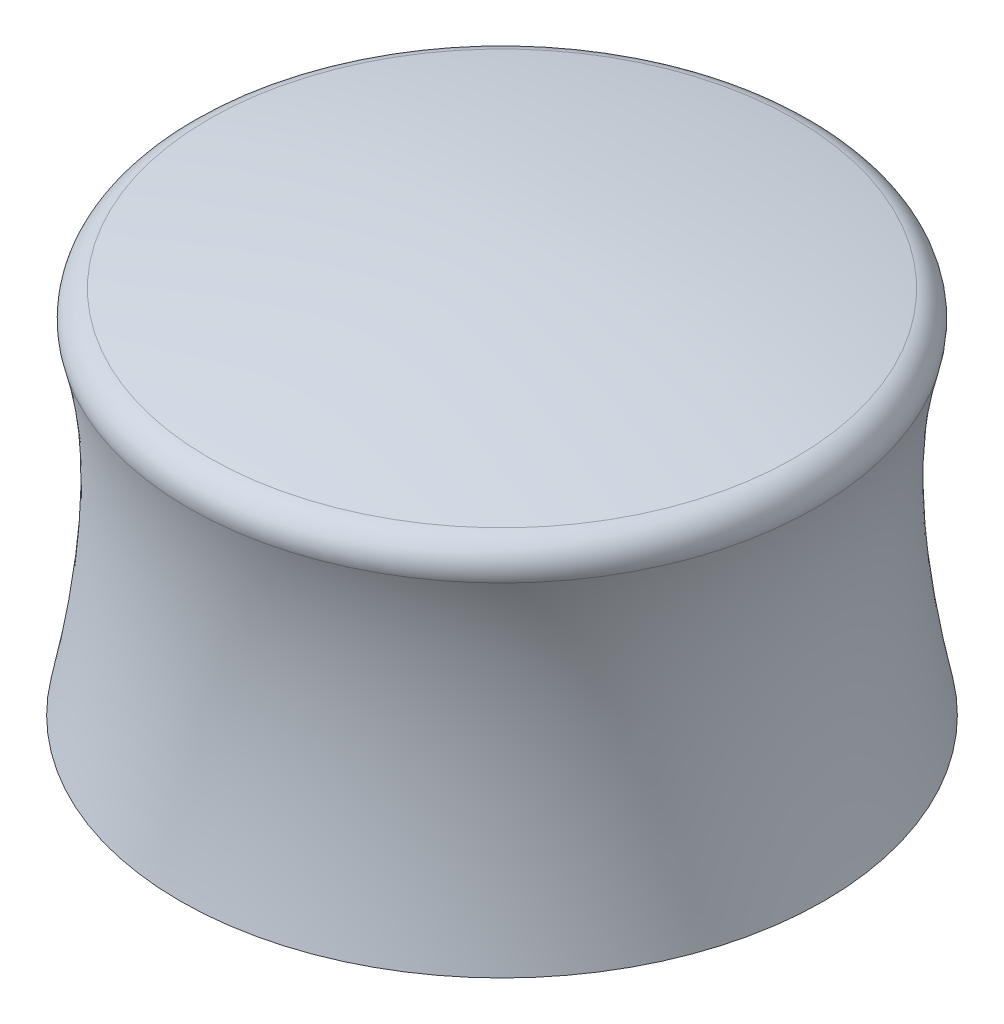
SolidWorks part; units mm, degrees
note: The reader was unsure of these and kept them because the rebuilt part matched: shared geometry of "Sketch4<3>".
ref_plane "Front Plane" through (0, 0, 0) normal (0, 0, 1) x (1, 0, 0)
ref_plane "Top Plane" through (0, 0, 0) normal (0, 1, 0) x (1, 0, 0)
ref_plane "Right Plane" through (0, 0, 0) normal (1, 0, 0) x (0, 0, -1)
sketch "Sketch1" plane through (0, 0, 0) normal (0, 1, 0) x (1, 0, 0)
  line L0 (0, 6) -> (-5.1962, -3) construction
  line L1 (-5.1962, -3) -> (5.1962, -3) construction
  line L2 (5.1962, -3) -> (0, 6) construction
  circle A0 centre (0, 0) radius 6 construction
  circle A1 centre (-5.1962, -3) radius 3
  circle A2 centre (0, 6) radius 3
  circle A3 centre (5.1962, -3) radius 3
  circle A4 centre (0, 0) radius 3 construction
  circle A5 centre (0, 0) radius 10
  dimension "D1" = 6
  dimension "D2" = 6
  dimension "D3" = 20
extrude "Boss-Extrude1" add sketch "Sketch1" against normal blind 1
sketch "Sketch3" plane through (0, 0, 0) normal (1, 0, 0) x (0, 0, -1)
  line L0 (0, 0) -> (0, 1.5) construction
  line L1 (0, 1.5) -> (-3.5896, 1.5) construction
  line L2 (0, 0) -> (0, -13.5) construction
  line L3 (2.1192, 1.5) -> (-2.1192, 1.5) construction
  line L4 (12, -13.5) -> (11, -13.5)
  line L5 (10, -1) -> (10, 0) construction
  line L6 (10, -1) -> (10, 0) construction
  line L7 (10.7861, -12.5231) -> (10.7861, -12.5231)
  line L8 (10.7861, -12.5231) -> (11, -13.5)
  line L9 (10, -0.5644) -> (10, 0)
  line L10 (10, 0) -> (0, 0)
  line L11 (0, 0) -> (0, 1.5)
  spline S0 degree 3 poles (0, 1.5) (5.2038, 1.5) (11.6669, 0.188) (12, 0) knots 0 0 0 0 1 1 1 1
  spline S1 degree 2 poles (12, 0) (10.1874, -4.8854) (12, -13.5) knots 0 0 0 1 1 1
  spline S2 degree 1 poles (0, 0.5) (10.7208, -0.7084) knots 0 0 1 1 construction
  spline S3 degree 1 poles (10.7208, -0.7084) (10.7861, -12.5231) knots 0 0 1 1 construction
  spline S4 degree 3 poles (0, 0.5) (0.4993, 0.5) (1.4857, 0.4761) (3.5535, 0.349) (5.6023, 0.1281) (7.48, -0.1341) (8.7603, -0.3383) (9.6808, -0.5025) (10.3208, -0.6261) (10.5828, -0.6794) (10.7208, -0.7084) knots 0 0 0 0 0.096843 0.193686 0.387372 0.484216 0.581059 0.677902 0.726323 0.774745 0.774745 0.774745 0.774745 only from (10, -0.5644) to (10.7208, -0.7084)
  spline S5 degree 2 poles (10.7208, -0.7084) (9.4354, -5.4148) (10.7861, -12.5231) knots 0.096446 0.096446 0.096446 0.931612 0.931612 0.931612
  dimension "D1" = 1.5
  dimension "D2" = 15
  dimension "D3" = 2
  dimension "D4" = 1
  dimension "D5" = 1
revolve "Revolve1" add sketch "Sketch3" angle 360 about L2
fillet "Fillet1" radius 1 1 edges at (0, 0, 12)
sketch "Sketch4" plane through (0, -1, 0) normal (0, -1, 0) x (1, 0, 0)
  circle A0 centre (0, 0) radius 3
  circle A1 centre (0, 0) radius 2
  dimension "D1" = 4
  dimension "D2" = 6
extrude "Boss-Extrude2" add sketch "Sketch4" along normal blind 11
extrude "Boss-Extrude3" add sketch "Sketch4<3>" along normal blind 10 contours A1
sketch "Sketch4<3>" plane through (0, -1, 0) normal (0, -1, 0) x (1, 0, 0) same geometry as "Sketch4"
